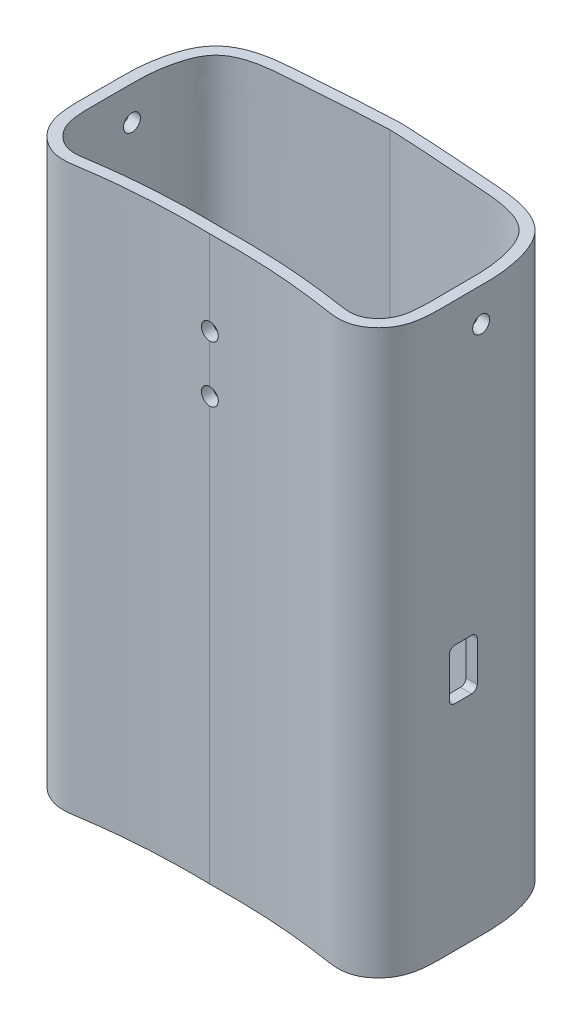
SolidWorks part; units mm, degrees
ref_plane "Ön Düzlem" through (0, 0, 0) normal (0, 0, 1) x (1, 0, 0)
ref_plane "Üst Düzlem" through (0, 0, 0) normal (0, 1, 0) x (1, 0, 0)
ref_plane "Sağ Düzlem" through (0, 0, 0) normal (1, 0, 0) x (0, 0, -1)
sketch "Çizim1" plane through (0, 0, 0) normal (0, 1, 0) x (1, 0, 0)
  line L0 (0, 17.9288) -> (0, -12.0712) construction
  line L1 (0, 0) -> (-30, 0) construction
  line L2 (-108.3091, -42.1463) -> (-63.9653, -42.1463) construction
  spline S0 degree 3 poles (0, 17.9288) (-5.8202, 17.7095) (-13.9034, 17.0426) (-26.8757, 16.196) (-29.5503, 8.9293) (-30.0905, 4.3361) (-29.9407, -0.8874) (-30.1549, -5.7017) (-29.6372, -10.9288) (-26.0312, -14.0818) (-15.7201, -12.3493) (-7.8072, -11.9389) (0, -12.0712) knots 0 0 0 0 0.19846 0.336013 0.394477 0.45973 0.505377 0.582751 0.635933 0.690009 0.731881 1 1 1 1
  spline S1 degree 3 poles (0, 17.9288) (5.8202, 17.7095) (13.9034, 17.0426) (26.8757, 16.196) (29.5503, 8.9293) (30.0905, 4.3361) (29.9407, -0.8874) (30.1549, -5.7017) (29.6372, -10.9288) (26.0312, -14.0818) (15.7201, -12.3493) (7.8072, -11.9389) (0, -12.0712) knots 0 0 0 0 0.19846 0.336013 0.394477 0.45973 0.505377 0.582751 0.635933 0.690009 0.731881 1 1 1 1
  spline S2 degree 1 poles (0, 19.9303) (0, -14.0714) knots 0 0 1 1 construction
  spline S3 degree 1 poles (0, 19.9303) (0, -14.0714) knots 0 0 1 1 construction
  spline S4 degree 3 poles (0, 19.9303) (-0.4569, 19.913) (-1.3788, 19.8761) (-3.1568, 19.7944) (-5.3169, 19.678) (-7.8418, 19.5195) (-11.19, 19.2895) (-14.5919, 19.03) (-18.2872, 18.7842) (-21.2619, 18.4861) (-24.2247, 17.8563) (-26.5803, 16.8232) (-28.2551, 15.5188) (-29.6889, 13.8306) (-30.7777, 11.4296) (-31.5143, 8.5883) (-31.9232, 5.825) (-32.0441, 3.0566) (-31.9879, 0.4286) (-32.0171, -2.0683) (-32.052, -4.7106) (-32.0036, -7.4061) (-31.6486, -10.0115) (-30.6275, -12.1561) (-29.5067, -13.557) (-28.1065, -14.6986) (-26.705, -15.3667) (-25.4582, -15.6359) (-24.2895, -15.7185) (-22.9553, -15.6032) (-21.6185, -15.3841) (-20.348, -15.2005) (-19.0747, -15.0274) (-17.3942, -14.8187) (-15.3102, -14.5944) (-12.8229, -14.3819) (-9.5026, -14.1699) (-6.1385, -14.0592) (-2.6849, -14.0381) (-0.8891, -14.0564) (0, -14.0714) knots -0.000856 -0.000856 -0.000856 -0.000856 0.014788 0.030433 0.061722 0.093011 0.1243 0.186877 0.218166 0.249455 0.280744 0.312033 0.327677 0.343322 0.37461 0.405899 0.437188 0.468477 0.499766 0.531055 0.562344 0.593633 0.624921 0.640566 0.65621 0.671855 0.687499 0.695321 0.703144 0.718788 0.734432 0.750077 0.765721 0.781366 0.812655 0.843944 0.875232 0.93781 0.969099 1.000388 1.000388 1.000388 1.000388
  spline S5 degree 3 poles (0, -14.0714) (0.8891, -14.0564) (2.6849, -14.0381) (6.1385, -14.0592) (9.5026, -14.1699) (12.8229, -14.3819) (15.3102, -14.5944) (17.3942, -14.8187) (19.0747, -15.0274) (20.348, -15.2005) (21.6185, -15.3841) (22.9553, -15.6032) (24.2895, -15.7185) (25.4582, -15.6359) (26.705, -15.3667) (28.1065, -14.6986) (29.5067, -13.557) (30.6275, -12.1561) (31.6486, -10.0115) (32.0036, -7.4061) (32.052, -4.7106) (32.0171, -2.0683) (31.9879, 0.4286) (32.0441, 3.0566) (31.9232, 5.825) (31.5143, 8.5883) (30.7777, 11.4296) (29.6889, 13.8306) (28.2551, 15.5188) (26.5803, 16.8232) (24.2247, 17.8563) (21.2619, 18.4861) (18.2872, 18.7842) (14.5919, 19.03) (11.19, 19.2895) (7.8418, 19.5195) (5.3169, 19.678) (3.1568, 19.7944) (1.3788, 19.8761) (0.4569, 19.913) (0, 19.9303) knots -0.000856 -0.000856 -0.000856 -0.000856 0.030433 0.061722 0.1243 0.155588 0.186877 0.218166 0.233811 0.249455 0.265099 0.280744 0.296388 0.304211 0.312033 0.327677 0.343322 0.358966 0.37461 0.405899 0.437188 0.468477 0.499766 0.531055 0.562344 0.593633 0.624921 0.65621 0.671855 0.687499 0.718788 0.750077 0.781366 0.812655 0.875232 0.906521 0.93781 0.969099 0.984743 1.000388 1.000388 1.000388 1.000388
  dimension "D1" = 30
  dimension "D2" = 30
  dimension "D3" = 2
extrude "Yükseklik-Ekstrüzyon1" add sketch "Çizim1" along normal blind 100
sketch "Çizim2" plane through (0, 100, 0) normal (0, 1, 0) x (1, 0, 0)
  line L0 (0, -14.0714) -> (0, -12.0712)
ref_plane "Düzlem1" through (0, 0, 14.0714) normal (0, 0, -1) x (-1, 0, 0)
sketch "Çizim3" plane through (0, 0, 14.0714) normal (0, 0, -1) x (-1, 0, 0)
  line L0 (0, 100) -> (0, 0) construction
  circle A0 centre (0, 85) radius 1.5
  circle A1 centre (0, 75) radius 1.5
  dimension "D1" = 10
  dimension "D3" = 3
  dimension "D2" = 15
extrude "Kes-Ekstrüzyon1" cut sketch "Çizim3" along normal blind 10
sketch "Çizim4" plane through (0, 0, 0) normal (0, -1, 0) x (1, 0, 0)
  spline S5 degree 3 poles (3998.4121, 83.4226) (-102.3546, -17.7812) (-29.2856, -21.2861) (3.1568, -19.7944) (5.3169, -19.678) (7.8418, -19.5195) (11.19, -19.2895) (14.5919, -19.03) (18.2872, -18.7842) (21.2619, -18.4861) (24.2247, -17.8563) (26.5803, -16.8232) (28.2551, -15.5188) (29.6889, -13.8306) (30.7777, -11.4296) (31.5143, -8.5883) (31.9232, -5.825) (32.0441, -3.0566) (31.9879, -0.4286) (32.0171, 2.0683) (32.052, 4.7106) (32.0036, 7.4061) (31.6486, 10.0115) (30.6275, 12.1561) (29.5067, 13.557) (28.1065, 14.6986) (26.705, 15.3667) (25.4582, 15.6359) (24.2895, 15.7185) (22.9553, 15.6032) (21.6185, 15.3841) (20.348, 15.2005) (19.0747, 15.0274) (17.3942, 14.8187) (15.3102, 14.5944) (12.8229, 14.3819) (9.5026, 14.1699) (6.1385, 14.0592) (-43.8501, 13.7536) (-145.9249, 35.9842) (3997.0667, -133.1935) knots -1.08014 -1.08014 -1.08014 -1.08014 0.014788 0.030433 0.061722 0.093011 0.1243 0.186877 0.218166 0.249455 0.280744 0.312033 0.327677 0.343322 0.37461 0.405899 0.437188 0.468477 0.499766 0.531055 0.562344 0.593633 0.624921 0.640566 0.65621 0.671855 0.687499 0.695321 0.703144 0.718788 0.734432 0.750077 0.765721 0.781366 0.812655 0.843944 0.875232 0.93781 0.969099 2.686743 2.686743 2.686743 2.686743 only from (0, -19.9303) to (0, 14.0714)
  spline S6 degree 3 poles (-3996.9772, -133.1899) (145.9234, 35.9838) (43.8498, 13.7536) (-6.1385, 14.0592) (-9.5026, 14.1699) (-12.8229, 14.3819) (-15.3102, 14.5944) (-17.3942, 14.8187) (-19.0747, 15.0274) (-20.348, 15.2005) (-21.6185, 15.3841) (-22.9553, 15.6032) (-24.2895, 15.7185) (-25.4582, 15.6359) (-26.705, 15.3667) (-28.1065, 14.6986) (-29.5067, 13.557) (-30.6275, 12.1561) (-31.6486, 10.0115) (-32.0036, 7.4061) (-32.052, 4.7106) (-32.0171, 2.0683) (-31.9879, -0.4286) (-32.0441, -3.0566) (-31.9232, -5.825) (-31.5143, -8.5883) (-30.7777, -11.4296) (-29.6889, -13.8306) (-28.2551, -15.5188) (-26.5803, -16.8232) (-24.2247, -17.8563) (-21.2619, -18.4861) (-18.2872, -18.7842) (-14.5919, -19.03) (-11.19, -19.2895) (-7.8418, -19.5195) (-5.3169, -19.678) (-3.1568, -19.7944) (29.2854, -21.2861) (102.3539, -17.7813) (-3998.3551, 83.4212) knots -1.687199 -1.687199 -1.687199 -1.687199 0.030433 0.061722 0.1243 0.155588 0.186877 0.218166 0.233811 0.249455 0.265099 0.280744 0.296388 0.304211 0.312033 0.327677 0.343322 0.358966 0.37461 0.405899 0.437188 0.468477 0.499766 0.531055 0.562344 0.593633 0.624921 0.65621 0.671855 0.687499 0.718788 0.750077 0.781366 0.812655 0.875232 0.906521 0.93781 0.969099 0.984743 2.079666 2.079666 2.079666 2.079666 only from (0, 14.0714) to (0, -19.9303)
  spline S7 degree 3 poles (0, -19.9303) (0.4569, -19.913) (1.3788, -19.8761) (3.1568, -19.7944) (5.3169, -19.678) (7.8418, -19.5195) (11.19, -19.2895) (14.5919, -19.03) (18.2872, -18.7842) (21.2619, -18.4861) (24.2247, -17.8563) (26.5803, -16.8232) (28.2551, -15.5188) (29.6889, -13.8306) (30.7777, -11.4296) (31.5143, -8.5883) (31.9232, -5.825) (32.0441, -3.0566) (31.9879, -0.4286) (32.0171, 2.0683) (32.052, 4.7106) (32.0036, 7.4061) (31.6486, 10.0115) (30.6275, 12.1561) (29.5067, 13.557) (28.1065, 14.6986) (26.705, 15.3667) (25.4582, 15.6359) (24.2895, 15.7185) (22.9553, 15.6032) (21.6185, 15.3841) (20.348, 15.2005) (19.0747, 15.0274) (17.3942, 14.8187) (15.3102, 14.5944) (12.8229, 14.3819) (9.5026, 14.1699) (6.1385, 14.0592) (2.6849, 14.0381) (0.8891, 14.0564) (0, 14.0714) knots -0.000856 -0.000856 -0.000856 -0.000856 0.014788 0.030433 0.061722 0.093011 0.1243 0.186877 0.218166 0.249455 0.280744 0.312033 0.327677 0.343322 0.37461 0.405899 0.437188 0.468477 0.499766 0.531055 0.562344 0.593633 0.624921 0.640566 0.65621 0.671855 0.687499 0.695321 0.703144 0.718788 0.734432 0.750077 0.765721 0.781366 0.812655 0.843944 0.875232 0.93781 0.969099 1.000388 1.000388 1.000388 1.000388
  spline S8 degree 3 poles (0, 14.0714) (-0.8891, 14.0564) (-2.6849, 14.0381) (-6.1385, 14.0592) (-9.5026, 14.1699) (-12.8229, 14.3819) (-15.3102, 14.5944) (-17.3942, 14.8187) (-19.0747, 15.0274) (-20.348, 15.2005) (-21.6185, 15.3841) (-22.9553, 15.6032) (-24.2895, 15.7185) (-25.4582, 15.6359) (-26.705, 15.3667) (-28.1065, 14.6986) (-29.5067, 13.557) (-30.6275, 12.1561) (-31.6486, 10.0115) (-32.0036, 7.4061) (-32.052, 4.7106) (-32.0171, 2.0683) (-31.9879, -0.4286) (-32.0441, -3.0566) (-31.9232, -5.825) (-31.5143, -8.5883) (-30.7777, -11.4296) (-29.6889, -13.8306) (-28.2551, -15.5188) (-26.5803, -16.8232) (-24.2247, -17.8563) (-21.2619, -18.4861) (-18.2872, -18.7842) (-14.5919, -19.03) (-11.19, -19.2895) (-7.8418, -19.5195) (-5.3169, -19.678) (-3.1568, -19.7944) (-1.3788, -19.8761) (-0.4569, -19.913) (0, -19.9303) knots -0.000856 -0.000856 -0.000856 -0.000856 0.030433 0.061722 0.1243 0.155588 0.186877 0.218166 0.233811 0.249455 0.265099 0.280744 0.296388 0.304211 0.312033 0.327677 0.343322 0.358966 0.37461 0.405899 0.437188 0.468477 0.499766 0.531055 0.562344 0.593633 0.624921 0.65621 0.671855 0.687499 0.718788 0.750077 0.781366 0.812655 0.875232 0.906521 0.93781 0.969099 0.984743 1.000388 1.000388 1.000388 1.000388
  dimension "D1" = 0
extrude "Yükseklik-Ekstrüzyon2" add sketch "Çizim4" against normal blind 4
ref_plane "Düzlem2" through (0, 73.5, 14.0714) normal (0, -1, 0) x (-1, 0, 0)
sketch "Çizim5" plane through (0, 73.5, 14.0714) normal (0, -1, 0) x (1, 0, 0)
  line L0 (0, -14.0714) -> (-28.4895, -14.0714)
  line L1 (-28.4895, -14.0714) -> (-57.0626, -14.0714)
ref_plane "Düzlem3" through (0, 0, 0) normal (-1, 0, 0) x (0, 0, -1)
sketch "Çizim6" plane through (0, 0, 0) normal (-1, 0, 0) x (0, 0, -1)
  line L0 (19.9303, 0) -> (-15.6852, 0) construction
  line L1 (-2.5714, -47) -> (0.4286, -47)
  line L2 (-3.5714, -46) -> (-3.5714, -39)
  line L3 (-2.5714, -38) -> (0.4286, -38)
  line L4 (1.4286, -46) -> (1.4286, -39)
  arc A0 (0.4286, -38) -> (1.4286, -39) centre (0.4286, -39) cw
  arc A1 (-3.5714, -39) -> (-2.5714, -38) centre (-2.5714, -39) cw
  arc A2 (-2.5714, -47) -> (-3.5714, -46) centre (-2.5714, -46) cw
  arc A3 (0.4286, -47) -> (1.4286, -46) centre (0.4286, -46) ccw
  point P9 (1.4286, -38)
  point P12 (-3.5714, -38)
  point P17 (1.4286, -47)
  dimension "D5" = 1
  dimension "D1" = 38
  dimension "D2" = 9
  dimension "D3" = 5
  dimension "D4" = 10.5
extrude "Kes-Ekstrüzyon2" cut sketch "Çizim6" against normal blind 44
sketch "Çizim7" plane through (0, 0, 0) normal (-1, 0, 0) x (0, 0, -1)
  line L0 (-15.6852, -100) -> (19.9303, -100) construction
  line L1 (2.1225, -100) -> (2.1225, -81.7237) construction
  circle A0 centre (2.1225, -94) radius 1.5
  point P2 (2.1225, -100)
  dimension "D1" = 6
extrude "Kes-Ekstrüzyon3" cut sketch "Çizim7" against normal blind 40 and the other way blind 40
